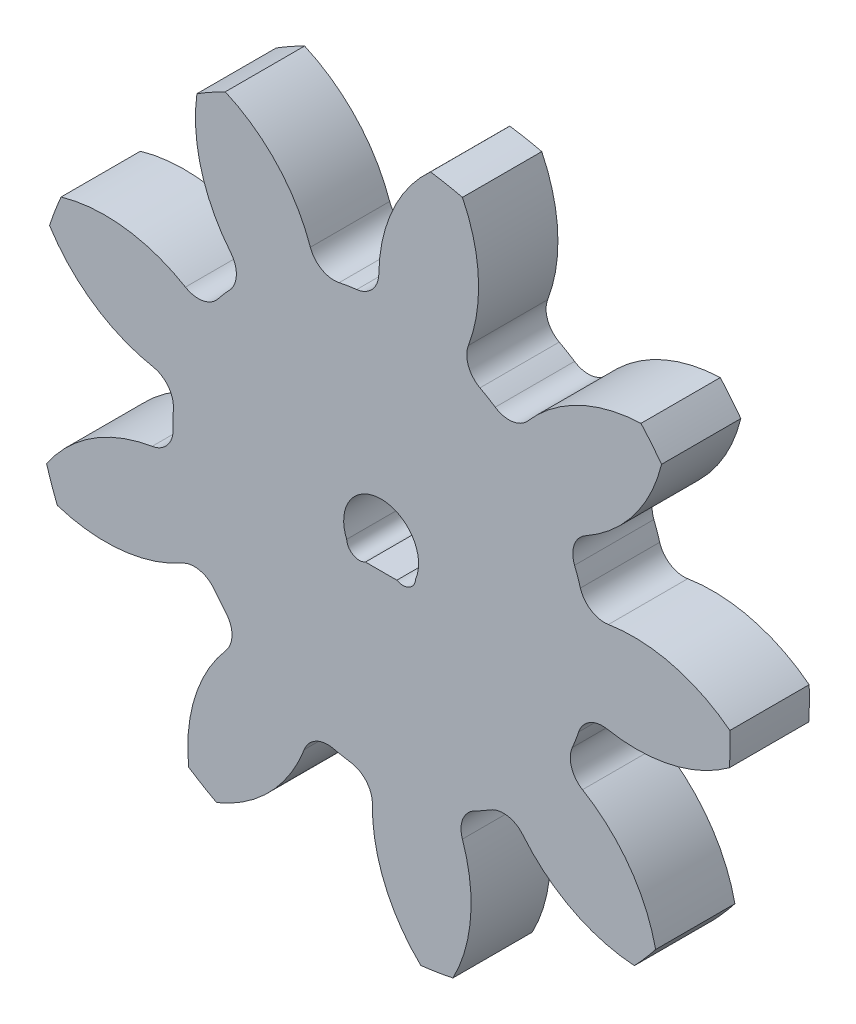
SolidWorks part; units mm, degrees
material "6061-T6 (SS)"
ref_plane "Front" through (0, 0, 0) normal (0, 0, 1) x (1, 0, 0)
ref_plane "Top" through (0, 0, 0) normal (0, 1, 0) x (1, 0, 0)
ref_plane "Right" through (0, 0, 0) normal (1, 0, 0) x (0, 0, -1)
sketch "Sketch3" plane through (0, 0, 0) normal (0, 0, 1) x (1, 0, 0)
  circle A0 centre (0, 0) radius 13.97
  dimension "od" = 27.94
extrude "gearBody" add sketch "Sketch3" along normal blind 3.175
sketch "Sketch2" plane through (0, 0, 0) normal (0, 0, 1) x (1, 0, 0)
  line L0 (0, 0) -> (10.2236, 4.2347) construction
  line L1 (10.8342, -11.8653) -> (0, 0) construction
  line L2 (0, 0) -> (36.3143, 0) construction
  line L3 (11.2576, -1.9775) -> (9.7312, -5.9958) construction
  line L5 (10.4944, -3.9867) -> (0, 0) construction
  line L7 (0, 0) -> (11.0659, 0) construction
  arc A0 (10.8784, -2.0289) -> (9.4816, -5.7056) centre (0, 0) ccw construction
  arc A1 (13.9443, -0.8463) -> (10.9892, -8.6255) centre (0, 0) ccw construction
  arc A2 (11.2576, -1.9775) -> (9.7312, -5.9958) centre (0, 0) ccw construction
  arc A3 (7.6546, -3.2888) -> (7.9075, -2.623) centre (0, 0) ccw
  arc A4 (10.8342, -11.8653) -> (8.0625, -4.5478) centre (4.8333, -9.9546) ccw
  arc A5 (10.8342, -11.8653) -> (15.9795, 1.6792) centre (0, 0) ccw
  arc A6 (15.9795, 1.6792) -> (9.0484, -1.9524) centre (10.2236, 4.2347) cw
  arc A7 (7.9075, -2.623) -> (9.0484, -1.9524) centre (8.861, -2.9393) cw
  arc A8 (8.0625, -4.5478) -> (7.6546, -3.2888) centre (8.5776, -3.6853) cw
  point P6 (15.9795, 1.6792)
  point P22 (10.8342, -11.8653)
  dimension "baseDia" = 22.1319
  dimension "od" = 27.94
  dimension "pd" = 22.86
  dimension "rd" = 16.6624
  dimension "rFillet" = 1.0046
  dimension "pointX" = 15.9795
  dimension "pointY" = 1.6792
  dimension "CTT" = 4.0183
  dimension "flankCenterAngle" = 22.5
extrude "toothCut" cut sketch "Sketch2" along normal through all
pattern_circular "CirPattern1" count 9 over 360 about axis through (0, 0, 3.175) along (0, 0, -1) of "toothCut"
ref_axis "toothSpace" through (0, 0, 0) along (0.9348, -0.3551, 0)
ref_axis "Axis2" through (10.5751, -9.1285, 0) along (-0.757, 0.6534, 0)
sketch "hub1Dia" plane through (0, 0, 0) normal (0, 0, -1) x (-1, 0, 0)
  circle A0 centre (0, 0) radius 12.7
  dimension "hub1Dia" = 25.4
sketch "hub2Dia" plane through (0, 0, 3.175) normal (0, 0, 1) x (1, 0, 0)
  circle A0 centre (0, 0) radius 12.7
  dimension "hub2dia" = 25.4
sketch "boreDia" plane through (0, 0, 0) normal (0, 0, 1) x (1, 0, 0)
  circle A0 centre (0, 0) radius 1.5
  dimension "boreDia" = 3
extrude "bore" cut sketch "boreDia" against normal mid plane 25400
sketch "kwy1sketch" plane through (0, 0, 0) normal (0, 0, 1) x (1, 0, 0)
  line L0 (-4.1066, 2.784) -> (0, 0) construction
  line L1 (29.3922, -4.5824) -> (15.1394, -25.6066)
  line L2 (15.1394, -25.6066) -> (-11.1409, -7.7906)
  line L3 (29.3922, -4.5824) -> (3.1119, 13.2336)
  line L4 (-11.1409, -7.7906) -> (0, 0)
  line L5 (0, 0) -> (3.1119, 13.2336)
  line L6 (0, 0) -> (7.7882, -2.9586) construction
  line L7 (22.2658, -15.0945) -> (0, 0) construction
  arc A7 (7.6546, -3.2888) -> (7.9075, -2.623) centre (0, 0) ccw construction
  point P9 (22.2658, -15.0945)
  point P13 (-0.685, 0.4644)
  dimension "kwy1width" = 25.4
  dimension "kwy1depth" = 26.9
  dimension "kwy1angle" = 13.333
  dimension "kwy1Depth2" = 31.75
sketch "kwy2sketch" plane through (0, 0, 0) normal (0, 0, 1) x (1, 0, 0)
  line L0 (7.7882, -2.9586) -> (0, 0) construction
  line L1 (0, 0) -> (-3.367, -0.6463) construction
  line L2 (24.0237, 17.5432) -> (28.8118, -7.4015)
  line L3 (28.8118, -7.4015) -> (-2.369, -13.3866)
  line L4 (24.0237, 17.5432) -> (-7.1571, 11.5581)
  line L5 (-2.369, -13.3866) -> (0, 0)
  line L6 (0, 0) -> (-7.1571, 11.5581)
  arc A2 (7.6546, -3.2888) -> (7.9075, -2.623) centre (0, 0) ccw construction
  point P10 (26.4177, 5.0708)
  dimension "kwy2angle" = 31.667
  dimension "kwy2Width" = 25.4
  dimension "kwy2depth" = 26.9
  dimension "kwy2Depth2" = 31.75
sketch "kwy3sketch" plane through (0, 0, 0) normal (0, 0, 1) x (1, 0, 0)
  line L0 (7.7882, -2.9586) -> (0, 0) construction
  line L1 (0, 0) -> (-1.3918, -2.053) construction
  line L2 (4.5824, 29.3922) -> (25.6066, 15.1394)
  line L3 (25.6066, 15.1394) -> (7.7906, -11.1409)
  line L4 (4.5824, 29.3922) -> (-13.2336, 3.1119)
  line L5 (7.7906, -11.1409) -> (0, 0)
  line L6 (-13.2336, 3.1119) -> (0, 0)
  point P10 (15.0945, 22.2658)
  dimension "kwy3angle" = 76.667
  dimension "kwy3depth" = 26.9
  dimension "kwy3width" = 25.4
  dimension "kwy3Depth2" = 31.75
sketch "kwy4sketch" plane through (0, 0, 0) normal (0, 0, 1) x (1, 0, 0)
  line L0 (7.7882, -2.9586) -> (0, 0) construction
  line L1 (0, 0) -> (0.3656, -1.9046) construction
  line L2 (7.4015, 28.8118) -> (-17.5432, 24.0237)
  line L3 (-17.5432, 24.0237) -> (-11.5581, -7.1571)
  line L4 (-11.5581, -7.1571) -> (0, 0)
  line L5 (13.3866, -2.369) -> (0, 0)
  line L6 (7.4015, 28.8118) -> (13.3866, -2.369)
  point P15 (-5.0708, 26.4177)
  dimension "kwy4angle" = 121.667
  dimension "kwy4depth" = 26.9
  dimension "kwy4width" = 25.4
  dimension "kwy4Depth2" = 31.75
sketch "kwy5sketch" plane through (0, 0, 0) normal (0, 0, 1) x (1, 0, 0)
  line L0 (7.7882, -2.9586) -> (0, 0) construction
  line L1 (0, 0) -> (1.3787, -0.9346) construction
  line L2 (-15.1394, 25.6066) -> (-29.3922, 4.5824)
  line L3 (-29.3922, 4.5824) -> (-3.1119, -13.2336)
  line L4 (-15.1394, 25.6066) -> (11.1409, 7.7906)
  line L5 (-3.1119, -13.2336) -> (0, 0)
  line L6 (11.1409, 7.7906) -> (0, 0)
  point P10 (-22.2658, 15.0945)
  dimension "kwy5width" = 25.4
  dimension "kwy5depth" = 26.9
  dimension "kwy5angle" = 166.667
  dimension "kwy5Depth2" = 31.75
sketch "kwy6sketch" plane through (0, 0, 0) normal (0, 0, 1) x (1, 0, 0)
  line L0 (7.7882, -2.9586) -> (0, 0) construction
  line L1 (0, 0) -> (1.6344, 0.3137) construction
  line L2 (-28.8118, 7.4015) -> (-24.0237, -17.5432)
  line L3 (-24.0237, -17.5432) -> (7.1571, -11.5581)
  line L4 (-28.8118, 7.4015) -> (2.369, 13.3866)
  line L5 (7.1571, -11.5581) -> (0, 0)
  line L6 (2.369, 13.3866) -> (0, 0)
  point P10 (-26.4177, -5.0708)
  dimension "kwy6angle" = 211.667
  dimension "kwy6width" = 25.4
  dimension "kwy6depth" = 26.9
  dimension "kwy6Depth2" = 31.75
sketch "kwy7sketch" plane through (0, 0, 0) normal (0, 0, 1) x (1, 0, 0)
  line L0 (7.7882, -2.9586) -> (0, 0) construction
  line L1 (0, 0) -> (1.0463, 1.5433) construction
  line L2 (-25.6066, -15.1394) -> (-4.5824, -29.3922)
  line L3 (-25.6066, -15.1394) -> (-7.7906, 11.1409)
  line L4 (-4.5824, -29.3922) -> (13.2336, -3.1119)
  line L5 (-7.7906, 11.1409) -> (0, 0)
  line L6 (13.2336, -3.1119) -> (0, 0)
  point P10 (-15.0945, -22.2658)
  dimension "kwy7angle" = 76.667
  dimension "kwy7width" = 25.4
  dimension "kwy7depth" = 26.9
  dimension "kwy7angle1" = 256.667
  dimension "kwy7Depth2" = 31.75
sketch "kwy8sketch" plane through (0, 0, 0) normal (0, 0, 1) x (1, 0, 0)
  line L0 (7.7882, -2.9586) -> (0, 0) construction
  line L1 (0, 0) -> (-0.3123, 1.6268) construction
  line L2 (-7.4015, -28.8118) -> (17.5432, -24.0237)
  line L3 (17.5432, -24.0237) -> (11.5581, 7.1571)
  line L4 (-7.4015, -28.8118) -> (-13.3866, 2.369)
  line L5 (11.5581, 7.1571) -> (0, 0)
  line L6 (-13.3866, 2.369) -> (0, 0)
  point P10 (5.0708, -26.4177)
  dimension "kwy8angle" = 301.667
  dimension "kwy8width" = 25.4
  dimension "kwy8depth" = 26.9
  dimension "kwy8Depth2" = 31.75
sketch "centerLine" plane through (0, 0, 0) normal (0, 1, 0) x (1, 0, 0)
  line L0 (0, 36.4807) -> (0, -59.6309) construction
ref_plane "CB1plane" through (0, 0, 0) normal (0, 0, -1) x (-1, 0, 0)
sketch "CB1diameter" plane through (0, 0, 0) normal (0, 0, -1) x (-1, 0, 0)
  circle A0 centre (0, 0) radius 12.7
  dimension "CB1diameter" = 25.4
ref_plane "CB2plane" through (0, 0, 3.175) normal (0, 0, 1) x (1, 0, 0)
sketch "CB2diameter" plane through (0, 0, 3.175) normal (0, 0, 1) x (1, 0, 0)
  circle A0 centre (0, 0) radius 12.7
  dimension "CB2diameter" = 25.4
ref_axis "Axis1" through (0, 0, 50) along (0, 0, -1)
sketch3d "3DSketch1" plane through (0, 0, 0) normal (0, 0, 1) x (1, 0, 0)
sketch "Sketch4" plane through (0, 0, 0) normal (0, 0, -1) x (-1, 0, 0)
  line L0 (1.118, -1) -> (-1.118, -1)
  circle A0 centre (0, 0) radius 1.5 construction
  arc A1 (-1.118, -1) -> (1.118, -1) centre (0, 0) ccw
  dimension "D1" = 1
extrude "Boss-Extrude1" add sketch "Sketch4" against normal up to surface (3.175 mm away) up to face at (1.5, 0, 3.175)
sketch "Sketch5" plane through (0, 0, 3.175) normal (0, 0, 1) x (1, 0, 0)
  line L0 (-1.118, -1) -> (-0.8734, -0.5548) construction
  line L1 (-0.8734, -0.5548) -> (-0.6288, -1) construction
  line L2 (-0.6288, -1) -> (-1.118, -1) construction
  line L3 (-1.118, -1) -> (-1.3804, -0.587) construction
  line L4 (-1.3804, -0.587) -> (-0.8734, -0.5548) construction
  line L5 (-0.8734, -0.5548) -> (-1.3804, -0.587) construction
  circle A0 centre (-0.8734, -0.5548) radius 0.508
  circle A1 centre (0.8734, -0.5548) radius 0.508
  arc A2 (1.118, -1) -> (-1.118, -1) centre (0, 0) ccw construction
  dimension "D1" = 0.508
extrude "Cut-Extrude1" cut sketch "Sketch5" against normal through all
